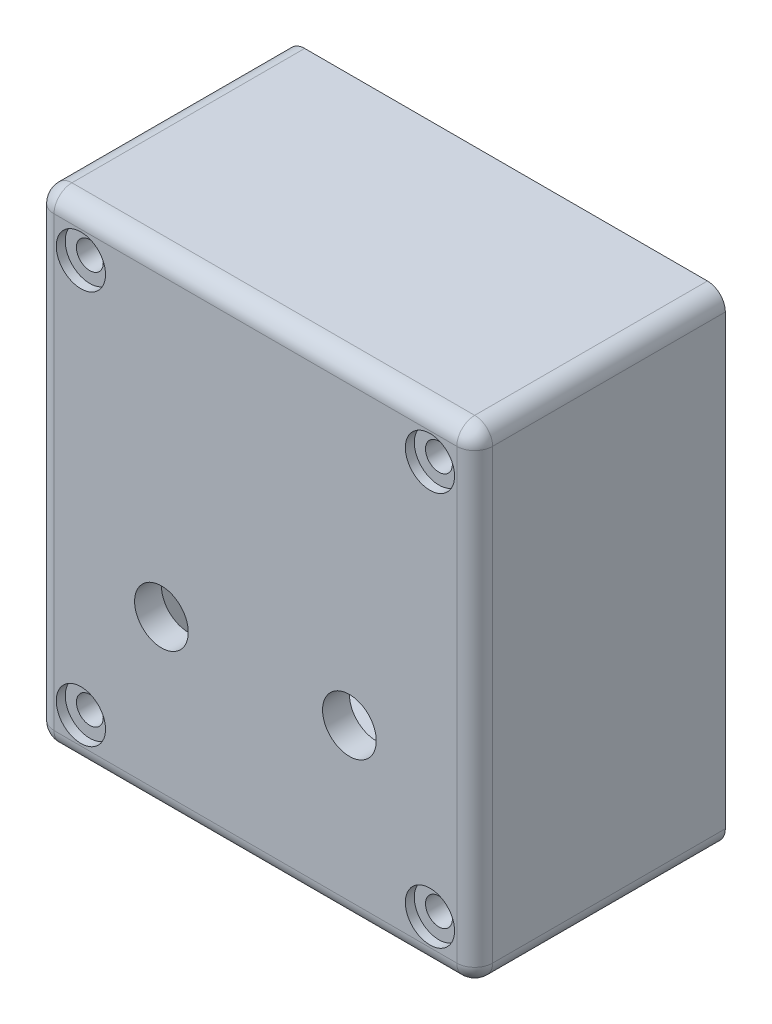
SolidWorks part; units mm, degrees
ref_plane "前视基准面" through (0, 0, 0) normal (0, 0, 1) x (1, 0, 0)
ref_plane "上视基准面" through (0, 0, 0) normal (0, 1, 0) x (1, 0, 0)
ref_plane "右视基准面" through (0, 0, 0) normal (1, 0, 0) x (0, 0, -1)
sketch "草图1" plane through (0, 0, 0) normal (0, 0, 1) x (1, 0, 0)
  line L1 (-20.5, -25) -> (20.5, -25)
  line L2 (-22.5, -23) -> (-22.5, 23)
  line L3 (-20.5, 25) -> (20.5, 25)
  line L4 (22.5, -23) -> (22.5, 23)
  line L5 (-22.5, -25) -> (22.5, 25) construction
  line L6 (-22.5, 25) -> (22.5, -25) construction
  line L7 (-22.5, -27) -> (22.5, -27)
  line L8 (-24.5, -25) -> (-24.5, 25)
  line L9 (-22.5, 27) -> (22.5, 27)
  line L10 (24.5, -25) -> (24.5, 25)
  line L11 (-24.5, -27) -> (24.5, 27) construction
  line L12 (-24.5, 27) -> (24.5, -27) construction
  arc A0 (-20.5, -25) -> (-22.5, -23) centre (-20.5, -23) cw
  arc A1 (20.5, -25) -> (22.5, -23) centre (20.5, -23) ccw
  arc A2 (-20.5, 25) -> (-22.5, 23) centre (-20.5, 23) ccw
  arc A3 (20.5, 25) -> (22.5, 23) centre (20.5, 23) cw
  arc A4 (24.5, 25) -> (22.5, 27) centre (22.5, 25) ccw
  arc A5 (24.5, -25) -> (22.5, -27) centre (22.5, -25) cw
  arc A6 (-22.5, -27) -> (-24.5, -25) centre (-22.5, -25) cw
  arc A7 (-24.5, 25) -> (-22.5, 27) centre (-22.5, 25) cw
  point P0 (0, 0)
  point P6 (0, 0)
  dimension "D5" = 2
  dimension "D1" = 50
  dimension "D2" = 45
  dimension "D3" = 54
  dimension "D4" = 49
extrude "凸台-拉伸1" add sketch "草图1" along normal blind 3 contours L10 A4 L9 A7 L8 A6 L7 A5
extrude "凸台-拉伸2" add sketch "草图1<3>" against normal blind 25
sketch "草图1<3>" plane through (0, 0, 0) normal (0, 0, 1) x (1, 0, 0) same geometry as "草图1"
sketch "草图3" plane through (0, 0, 0) normal (0, 0, -1) x (-1, 0, 0)
  line L1 (-19.5, -22) -> (19.5, -22) construction
  line L2 (-19.5, -22) -> (-19.5, 22) construction
  line L3 (-19.5, 22) -> (19.5, 22) construction
  line L4 (19.5, -22) -> (19.5, 22) construction
  line L5 (-19.5, -22) -> (19.5, 22) construction
  line L6 (-19.5, 22) -> (19.5, -22) construction
  circle A0 centre (19.5, 22) radius 1.5
  circle A2 centre (19.5, -22) radius 1.5
  circle A3 centre (-19.5, -22) radius 1.5
  circle A4 centre (-19.5, 22) radius 1.5
  point P0 (0, 0)
  dimension "D3" = 3
  dimension "D1" = 44
  dimension "D2" = 39
extrude "切除-拉伸1" cut sketch "草图3" against normal through all
sketch "草图4" plane through (0, 0, 3) normal (0, 0, 1) x (1, 0, 0)
  circle A0 centre (-19.5, 22) radius 2.75
  circle A1 centre (19.5, 22) radius 2.75
  circle A2 centre (19.5, -22) radius 2.75
  circle A3 centre (-19.5, -22) radius 2.75
  dimension "D1" = 5.5
  dimension "D2" = 5.5
  dimension "D3" = 5.5
  dimension "D4" = 5.5
extrude "切除-拉伸2" cut sketch "草图4" against normal blind 1
sketch "草图5" plane through (0, 0, 0) normal (0, 0, -1) x (-1, 0, 0)
  line L0 (0, 0) -> (0, 31.1574) construction
  line L1 (-16.5, 17) -> (16.5, 17)
  line L2 (-16.5, 17) -> (-16.5, 23)
  line L3 (-16.5, 23) -> (16.5, 23)
  line L4 (16.5, 17) -> (16.5, 23)
  line L5 (-16.5, 17) -> (16.5, 23) construction
  line L6 (-16.5, 23) -> (16.5, 17) construction
  line L7 (-20.5, 25) -> (20.5, 25) construction
  point P0 (0, 20)
  dimension "D1" = 33
  dimension "D2" = 2
  dimension "D3" = 6
extrude "切除-拉伸3" cut sketch "草图5" against normal blind 1.5
sketch "草图6" plane through (0, -25, 0) normal (0, 1, 0) x (1, 0, 0)
  line L0 (-16.0524, 7.5) -> (14.1191, 7.5) construction
  line L1 (22.5, 0) -> (-22.5, 0) construction
  line L2 (2.5, 7.5) -> (-5.5, 7.5)
  line L3 (3.5, 8.5) -> (3.5, 10.5)
  line L4 (2.5, 11.5) -> (-5.5, 11.5)
  line L5 (-6.5, 8.5) -> (-6.5, 10.5)
  line L6 (-22.5, 0) -> (-22.5, 19.7707) construction
  line L7 (17.8808, 9) -> (-17.4737, 9) construction
  line L9 (7, 9) -> (12, 9)
  line L10 (7, 9) -> (7, 12)
  line L11 (7, 12) -> (12, 12)
  line L12 (12, 9) -> (12, 12)
  arc A0 (2.5, 11.5) -> (3.5, 10.5) centre (2.5, 10.5) cw
  arc A1 (3.5, 8.5) -> (2.5, 7.5) centre (2.5, 8.5) cw
  arc A2 (-5.5, 7.5) -> (-6.5, 8.5) centre (-5.5, 8.5) cw
  arc A3 (-6.5, 10.5) -> (-5.5, 11.5) centre (-5.5, 10.5) cw
  point P10 (0, 0)
  point P13 (3.5, 11.5)
  point P16 (3.5, 7.5)
  point P19 (-6.5, 7.5)
  point P22 (-6.5, 11.5)
  dimension "D6" = 1
  dimension "D1" = 7.5
  dimension "D2" = 4
  dimension "D3" = 10
  dimension "D4" = 45
  dimension "D5" = 16
  dimension "D7" = 9
  dimension "D8" = 3
  dimension "D9" = 29.5
  dimension "D10" = 5
extrude "切除-拉伸4" cut sketch "草图6" against normal through all
fillet "圆角1" radius 2 8 edges at (-23.9142, 26.4142, 3) (-24.5, 0, 3) (-23.9142, -26.4142, 3) (0, -27, 3) (23.9142, -26.4142, 3) (24.5, 0, 3) (23.9142, 26.4142, 3) (0, 27, 3)
sketch "草图7" plane through (0, 0, 0) normal (0, 0, -1) x (-1, 0, 0)
  line L0 (0, 25) -> (0, -8) construction
  line L1 (-20.5, 25) -> (20.5, 25) construction
  line L2 (-10.5, -8) -> (10.5, -8) construction
  line L4 (-22.5, -23) -> (-22.5, 23) construction
  circle A0 centre (-10.5, -8) radius 3
  circle A1 centre (10.5, -8) radius 3
  point P8 (0, -8)
  dimension "D3" = 6
  dimension "D4" = 6
  dimension "D1" = 33
  dimension "D2" = 12
extrude "切除-拉伸5" cut sketch "草图7" against normal through all
